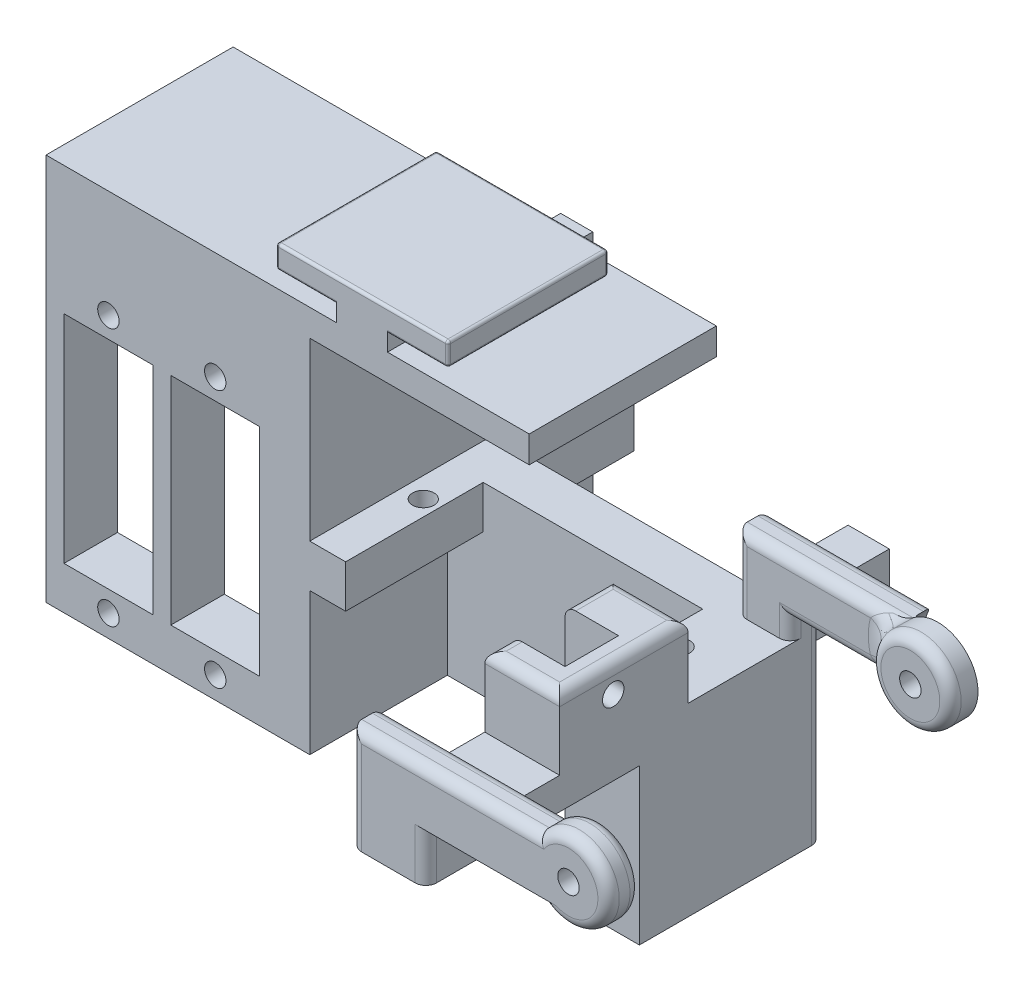
SolidWorks part; units mm, degrees
ref_plane "Front Plane" through (0, 0, 0) normal (0, 0, 1) x (1, 0, 0)
ref_plane "Top Plane" through (0, 0, 0) normal (0, 1, 0) x (1, 0, 0)
ref_plane "Right Plane" through (0, 0, 0) normal (1, 0, 0) x (0, 0, -1)
sketch "Sketch1" plane through (0, 0, 0) normal (0, 0, 1) x (1, 0, 0)
  line L1 (-10.82, 18.1) -> (10.82, 18.1)
  line L2 (-10.82, 18.1) -> (-10.82, -18.1)
  line L3 (-10.82, -18.1) -> (10.82, -18.1)
  line L4 (10.82, 18.1) -> (10.82, -18.1)
  line L5 (-10.82, 18.1) -> (10.82, -18.1) construction
  line L6 (-10.82, -18.1) -> (10.82, 18.1) construction
  point P0 (0, 0)
  dimension "D1" = 21.64
  dimension "D2" = 36.2
extrude "Center Column" add sketch "Sketch1" along normal mid plane 5
sketch "Sketch2" plane through (-10.82, 0, 0) normal (-1, 0, 0) x (0, 0, 1)
  line L0 (-2.5, 18.1) -> (-14.98, 18.1)
  line L1 (-14.98, 18.1) -> (-14.98, 15.6)
  line L2 (-14.98, 15.6) -> (-10.5, 15.6)
  line L3 (-10.5, 15.6) -> (-2.5, 10.98)
  line L4 (-2.5, 18.1) -> (-2.5, -18.1) construction
  line L6 (-2.5, 10.98) -> (2.5, 10.98)
  line L7 (2.5, 18.1) -> (2.5, -18.1) construction
  line L8 (2.5, 10.98) -> (2.5, 18.1)
  line L9 (2.5, 18.1) -> (-2.5, 18.1)
  dimension "D1" = 12.48
  dimension "D2" = 2.5
  dimension "D3" = 4.48
  dimension "D4" = 7.12
extrude "Column Cap" add sketch "Sketch2" against normal blind 55.14
sketch "Sketch5" plane through (0, 0, 2.5) normal (0, 0, 1) x (1, 0, 0)
  line L0 (16.33, 18.1) -> (21.08, 18.1)
  line L1 (44.32, 18.1) -> (-10.82, 18.1) construction
  line L2 (21.08, 18.1) -> (21.08, 19.6)
  line L3 (21.08, 19.6) -> (26.74, 19.6)
  line L4 (26.74, 19.6) -> (26.74, 21.75)
  line L5 (26.74, 21.75) -> (10.67, 21.75)
  line L6 (10.67, 21.75) -> (10.67, 19.6)
  line L7 (10.67, 19.6) -> (16.33, 19.6)
  line L8 (16.33, 19.6) -> (16.33, 18.1)
  dimension "D1" = 4.75
  dimension "D2" = 5.66
  dimension "D3" = 5.66
  dimension "D4" = 2.15
  dimension "D5" = 1.5
  dimension "D6" = 2.15
  dimension "D7" = 27.15
extrude "Attachment Block" add sketch "Sketch5" against normal blind 14.98
sketch "Sketch6" plane through (10.82, 0, 0) normal (1, 0, 0) x (0, 0, -1)
  line L0 (-2.5, -18.1) -> (-2.5, -3.6)
  line L1 (-2.5, -18.1) -> (-2.5, 10.98) construction
  line L2 (-2.5, -3.6) -> (2.5, -3.6)
  line L3 (2.5, -18.1) -> (2.5, 10.98) construction
  line L4 (2.5, -3.6) -> (2.5, -18.1)
  line L5 (2.5, -18.1) -> (-2.5, -18.1)
  dimension "D1" = 14.5
extrude "Central Extrusion" add sketch "Sketch6" along normal blind 33.792
sketch "Sketch7" plane through (0, 0, -2.5) normal (0, 0, -1) x (-1, 0, 0)
  line L0 (-10.82, -3.6) -> (-10.82, -0.8181)
  line L1 (-10.82, -3.6) -> (-10.82, 10.98) construction
  line L4 (-34.92, -0.8181) -> (-10.82, -0.8181)
  line L6 (-44.612, -18.1) -> (-10.82, -18.1)
  line L7 (10.82, -18.1) -> (-44.612, -18.1) construction
  line L8 (-10.82, -18.1) -> (-10.82, -3.6)
  line L10 (-44.612, -3.6) -> (-10.82, -3.6) construction
  line L11 (-34.92, -0.8181) -> (-44.612, -0.8181)
  line L12 (-44.612, -0.8181) -> (-44.612, -18.1)
  line L13 (-44.612, -18.1) -> (-40.254, -18.1)
  line M10 (-10.82, 10.98) -> (-10.82, -3.6)
  line M11 (-10.82, -3.6) -> (-44.612, -3.6)
  dimension "D1" = 24.1
  dimension "D2" = 2.7819
  dimension "D3" = 4.358
extrude "Wing Extrusion" add sketch "Sketch7" along normal mid plane 0.89 contours L4 M11 M10 | L6 L8 M11 region at (27.716, -2.2091, -2.5) region at (27.716, -10.85, -2.5)
sketch "Sketch10" plane through (0, 0, -2.945) normal (0, 0, -1) x (-1, 0, 0)
  line L0 (-10.82, -0.8181) -> (-10.82, -9.8181)
  line L1 (-10.82, -9.8181) -> (-14.67, -9.8181)
  line L2 (-14.67, -9.8181) -> (-14.67, -0.8181)
  line L3 (-10.82, -0.8181) -> (-44.612, -0.8181) construction
  line L4 (-14.67, -0.8181) -> (-10.82, -0.8181)
  dimension "D1" = 9
  dimension "D2" = 3.85
extrude "Servo Tab Extrusion" add sketch "Sketch10" along normal blind 9.48
sketch "Sketch11" plane through (0, 0, -2.945) normal (0, 0, -1) x (-1, 0, 0)
  line L0 (-44.612, -0.8181) -> (-44.612, -18.1)
  line L1 (-14.67, -0.8181) -> (-44.612, -0.8181) construction
  line L2 (-44.612, -18.1) -> (-10.82, -18.1) construction
  line L3 (-44.612, -18.1) -> (-34.67, -18.1)
  line L4 (-34.67, -18.1) -> (-34.67, -0.8181)
  line L5 (-34.67, -0.8181) -> (-44.612, -0.8181)
  dimension "D1" = 20
  dimension "D2" = 0
extrude "Front Tab Extrusion" add sketch "Sketch11" along normal blind 11.63
sketch "Sketch15" plane through (0, 0, -2.055) normal (0, 0, 1) x (1, 0, 0)
  line L0 (37.612, -3.6) -> (47.612, -3.6)
  line L1 (10.82, -3.6) -> (44.612, -3.6) construction
  line L2 (47.612, -3.6) -> (47.612, 5.9)
  line L3 (47.612, 5.9) -> (37.612, 5.9)
  line L4 (37.612, 5.9) -> (37.612, -3.6)
  dimension "D1" = 7
  dimension "D2" = 10
  dimension "D3" = 9.5
extrude "Center Block" add sketch "Sketch15" along normal blind 12
sketch "Sketch16" plane through (37.612, 0, 0) normal (-1, 0, 0) x (0, 0, 1)
  line L0 (2.445, 5.9) -> (2.445, 0.47)
  line L1 (9.945, 5.9) -> (-2.055, 5.9) construction
  line L2 (2.445, 0.47) -> (7.445, 0.47)
  line L3 (7.445, 0.47) -> (7.445, 5.9)
  line L4 (2.445, 5.9) -> (7.445, 5.9)
  line L5 (-2.055, 5.9) -> (-2.055, -0.8181) construction
  dimension "D1" = 4.5
  dimension "D2" = 5
  dimension "D3" = 5.43
extrude "Center Chasm" cut sketch "Sketch16" against normal blind 5
sketch "Sketch17" plane through (42.612, 0, 0) normal (-1, 0, 0) x (0, 0, 1)
  line L0 (7.445, 5.9) -> (2.445, 5.9) construction
  line L1 (2.445, 5.9) -> (2.445, 0.47) construction
  circle A0 centre (4.945, 3.4) radius 1
  dimension "D1" = 2
  dimension "D2" = 2.5
  dimension "D3" = 2.5
extrude "Center Hole" cut sketch "Sketch17" against normal through all
sketch "Sketch18" plane through (0, 0, 9.945) normal (0, 0, 1) x (1, 0, 0)
  line L1 (47.612, -3.6) -> (47.612, 5.9) construction
  line L2 (47.612, -0.6488) -> (37.612, -0.6488)
  line L3 (37.612, 5.9) -> (37.612, -3.6) construction
  line L4 (37.612, -0.6488) -> (37.612, -3.6)
  line L6 (37.612, -3.6) -> (47.612, -3.6)
  line L7 (47.612, -3.6) -> (47.612, -0.6488)
  dimension "D1" = 2.9512
extrude "Holder Arm" add sketch "Sketch18" along normal blind 12.5
sketch "Sketch19" plane through (0, -0.6488, 0) normal (0, 1, 0) x (1, 0, 0)
  line L1 (37.612, -22.445) -> (37.612, -9.945) construction
  line L7 (37.612, -19.445) -> (37.612, -22.445)
  line L8 (37.612, -22.445) -> (47.612, -22.445)
  line L11 (37.612, -19.445) -> (47.612, -19.445)
  line L12 (47.612, -19.445) -> (47.612, -22.445)
  line L13 (47.612, -22.445) -> (47.612, -9.945) construction
  dimension "D1" = 3
extrude "Elbow Extrusion" add sketch "Sketch19" along normal blind 6.78
sketch "Sketch27" plane through (47.612, 0, 0) normal (1, 0, 0) x (0, 0, -1)
  line L0 (-22.445, 6.1312) -> (-22.445, 1.1312)
  line L1 (-22.445, -3.6) -> (-22.445, 6.1312) construction
  line L2 (-22.445, 1.1312) -> (-19.445, 1.1312)
  line L3 (-19.445, 6.1312) -> (-19.445, -0.6488) construction
  line L4 (-19.445, 1.1312) -> (-19.445, 6.1312)
  line L5 (-19.445, 6.1312) -> (-22.445, 6.1312)
  dimension "D1" = 5
extrude "Forearm Extrusion" add sketch "Sketch27" along normal blind 7.874
sketch "Sketch28" plane through (0, 0, 22.445) normal (0, 0, 1) x (1, 0, 0)
  circle A0 centre (57.932, 3.6312) radius 1
  circle A1 centre (57.932, 3.6312) radius 3.75
  dimension "D1" = 2
  dimension "D4" = 7.5
  dimension "D2" = 20.32
  dimension "D3" = 2.5
extrude "Hand Extrusion" add sketch "Sketch28" against normal up to surface (3 mm away) up to face at (46.9033, 2.2045, 19.445)
sketch "Sketch23" plane through (0, -0.8181, 0) normal (0, 1, 0) x (1, 0, 0)
  line L1 (44.612, 14.575) -> (39.612, 14.575)
  line L2 (44.612, 14.575) -> (44.612, 11.575)
  line L3 (44.612, 11.575) -> (39.612, 11.575)
  line L4 (39.612, 14.575) -> (39.612, 11.575)
  dimension "D1" = 5
  dimension "D2" = 3
extrude "Right Elbow Extrusion" add sketch "Sketch23" along normal blind 6.902
sketch "Sketch24" plane through (44.612, 0, 0) normal (1, 0, 0) x (0, 0, -1)
  line L0 (11.575, 6.0839) -> (14.575, 6.0839)
  line L1 (14.575, 6.0839) -> (14.575, 1.0839)
  line L2 (14.575, 6.0839) -> (14.575, -18.1) construction
  line L3 (14.575, 1.0839) -> (11.575, 1.0839)
  line L4 (11.575, 6.0839) -> (11.575, -0.8181) construction
  line L5 (11.575, 1.0839) -> (11.575, 6.0839)
  dimension "D1" = 5
extrude "Right Forearm Extrusion" add sketch "Sketch24" along normal blind 11
sketch "Sketch25" plane through (0, 0, -14.575) normal (0, 0, -1) x (-1, 0, 0)
  line L1 (-34.67, -18.1) -> (-34.67, -0.8181) construction
  circle A0 centre (-57.87, 3.5839) radius 1
  circle A1 centre (-57.87, 3.5839) radius 3.75
  dimension "D2" = 2
  dimension "D4" = 7.5
  dimension "D1" = 23.2
  dimension "D3" = 2.5
extrude "Right Hand" add sketch "Sketch25" against normal blind 5.02
sketch "Sketch26" plane through (0, 0, -2.5) normal (0, 0, -1) x (-1, 0, 0)
  line L0 (10.82, 10.98) -> (10.82, -18.1) construction
  line L1 (0.84, 6.1) -> (9.14, 6.1)
  line L2 (0.84, 6.1) -> (0.84, -14.1)
  line L3 (0.84, -14.1) -> (9.14, -14.1)
  line L4 (9.14, 6.1) -> (9.14, -14.1)
  line L5 (-9.14, 6.1) -> (-0.84, 6.1)
  line L6 (-9.14, 6.1) -> (-9.14, -14.1)
  line L7 (-9.14, -14.1) -> (-0.84, -14.1)
  line L8 (-0.84, 6.1) -> (-0.84, -14.1)
  line L9 (10.82, 10.98) -> (-10.82, 10.98) construction
  circle A0 centre (-4.99, 8.05) radius 1
  circle A1 centre (4.99, 8.05) radius 1
  circle A2 centre (-4.99, -16.05) radius 1
  circle A3 centre (4.99, -16.05) radius 1
  dimension "D9" = 2
  dimension "D10" = 2
  dimension "D11" = 2
  dimension "D12" = 2
  dimension "D1" = 1.68
  dimension "D2" = 4.88
  dimension "D3" = 20.2
  dimension "D4" = 8.3
  dimension "D5" = 1.68
  dimension "D6" = 8.3
  dimension "D7" = 4.88
  dimension "D8" = 20.2
  dimension "D13" = 4.15
  dimension "D14" = 1.95
  dimension "D15" = 1.95
  dimension "D16" = 4.15
  dimension "D17" = 1.95
  dimension "D18" = 4.15
  dimension "D19" = 1.95
  dimension "D20" = 4.15
extrude "Rear Servo Mounts" cut sketch "Sketch26" against normal through all
sketch "Sketch29" plane through (10.82, 0, 0) normal (1, 0, 0) x (0, 0, -1)
  line L1 (-2.5, 10.98) -> (19.745, 10.98)
  line L2 (2.945, -18.1) -> (19.745, -18.1)
  line L3 (19.745, -18.1) -> (19.745, 10.98)
  line L4 (-2.5, 10.98) -> (-2.5, -18.1)
  line L5 (-2.5, -18.1) -> (2.945, -18.1)
  dimension "D2" = 16.8
extrude "New Back" add sketch "Sketch29" along normal blind 3
sketch "Sketch30" plane through (0, -18.1, 0) normal (0, -1, 0) x (1, 0, 0)
  line L10 (10.82, -19.745) -> (13.82, -19.745)
  line L11 (10.82, -19.745) -> (13.82, -19.745)
  line L12 (13.82, -19.745) -> (13.82, -2.945)
  line L13 (13.82, -19.745) -> (13.82, -2.945)
  line L14 (44.612, 2.5) -> (-10.82, 2.5)
  line L19 (-10.82, 2.5) -> (-10.82, -2.5)
  line L20 (-10.82, -2.5) -> (10.82, -2.5)
  line L21 (10.82, -2.5) -> (10.82, -19.745)
  line L24 (13.82, -2.945) -> (34.67, -2.945)
  line L25 (34.67, -2.945) -> (34.67, -14.575)
  line L26 (34.67, -14.575) -> (44.612, -14.575)
  line L27 (44.612, -14.575) -> (44.612, 2.5)
  line L28 (44.612, 2.5) -> (-10.82, 2.5)
  line L33 (-10.82, 2.5) -> (-10.82, -2.5)
  line L34 (-10.82, -2.5) -> (10.82, -2.5)
  line L35 (10.82, -2.5) -> (10.82, -19.745)
  line L38 (13.82, -2.945) -> (34.67, -2.945)
  line L39 (34.67, -2.945) -> (34.67, -14.575)
  line L40 (34.67, -14.575) -> (44.612, -14.575)
  line L41 (44.612, -14.575) -> (44.612, 2.5)
  dimension "D1" = 0
extrude "Bottom Support" add sketch "Sketch30" along normal blind 3
sketch "Sketch31" plane through (34.67, 0, 0) normal (-1, 0, 0) x (0, 0, 1)
  line L0 (-14.575, -0.8181) -> (-2.945, -0.8181)
  line L1 (-2.945, -0.8181) -> (-2.945, -21.1)
  line L2 (-2.945, -21.1) -> (-14.575, -21.1)
  line L3 (-14.575, -21.1) -> (-14.575, -0.8181)
extrude "Re-cut Central Cavity" cut sketch "Sketch31" against normal blind 3
sketch "Sketch32" plane through (14.67, 0, 0) normal (1, 0, 0) x (0, 0, -1)
  line L4 (2.945, -0.8181) -> (2.945, -9.8181)
  line L5 (2.945, -9.8181) -> (12.425, -9.8181)
  line L6 (12.425, -9.8181) -> (12.425, -0.8181)
  line L7 (12.425, -0.8181) -> (2.945, -0.8181)
  line L8 (2.945, -0.8181) -> (2.945, -9.8181)
  line L9 (2.945, -9.8181) -> (12.425, -9.8181)
  line L10 (12.425, -9.8181) -> (12.425, -0.8181)
  line L11 (12.425, -0.8181) -> (2.945, -0.8181)
  dimension "D1" = 0
extrude "Form Left Front-Rear Block" add sketch "Sketch32" along normal blind 3
sketch "Sketch33" plane through (0, 0, -2.945) normal (0, 0, -1) x (-1, 0, 0)
  line L0 (-37.67, -0.8181) -> (-37.67, -18.1)
  line L1 (-37.67, -21.1) -> (-37.67, -0.8181) construction
  line L2 (-37.67, -0.8181) -> (-17.67, -0.8181)
  line L3 (-17.67, -0.8181) -> (-17.67, -18.1)
  line L4 (-17.67, -18.1) -> (-37.67, -18.1)
  dimension "D1" = 3
extrude "Create Center Cavity" cut sketch "Sketch33" against normal through all
sketch "Sketch34" plane through (13.82, 0, 0) normal (1, 0, 0) x (0, 0, -1)
  line L0 (12.425, -0.8181) -> (2.055, -0.8181) construction
  line L1 (12.425, -0.8181) -> (10.355, -0.8181)
  line L2 (12.425, -0.8181) -> (12.425, -21.1)
  line L6 (10.355, -0.8181) -> (10.355, -21.1)
  line L7 (19.745, -21.1) -> (2.945, -21.1) construction
  line L8 (10.355, -21.1) -> (12.425, -21.1)
  dimension "D1" = 8.3
  dimension "D2" = 0
extrude "Boss-Extrude6" add sketch "Sketch34" along normal up to surface (23.85 mm away) up to face at (37.67, -9.7838, 1.4217)
sketch "Sketch35" plane through (0, 0, -12.425) normal (0, 0, -1) x (-1, 0, 0)
  line L0 (-13.82, -0.8181) -> (-13.82, -21.1)
  line L4 (-13.82, 10.98) -> (-13.82, -0.8181)
  line L6 (-13.82, 10.98) -> (-10.82, 10.98)
  line L7 (-10.82, 10.98) -> (-10.82, -21.1)
  line L8 (-10.82, -21.1) -> (-13.82, -21.1)
  dimension "D1" = 3
extrude "Extend Wing Extrusion" add sketch "Sketch35" along normal blind 10.6532
sketch "Sketch37" plane through (0, 0, -12.425) normal (0, 0, -1) x (-1, 0, 0)
  line L0 (-13.82, -0.8181) -> (-13.82, -9.8181)
  line L1 (-13.82, -21.1) -> (-13.82, -0.8181) construction
  line L2 (-13.82, -9.8181) -> (-17.67, -9.8181)
  line L3 (-17.67, -9.8181) -> (-17.67, -0.8181)
  line L4 (-13.82, -0.8181) -> (-37.67, -0.8181) construction
  line L5 (-17.67, -0.8181) -> (-13.82, -0.8181)
  dimension "D1" = 9
  dimension "D2" = 3.85
extrude "Right Front-Rear Extrusion" add sketch "Sketch37" along normal blind 9.48
sketch "Sketch38" plane through (0, 5.9, 0) normal (0, 1, 0) x (1, 0, 0)
  line L0 (47.612, -9.945) -> (47.612, 2.055)
  line L1 (47.612, 2.055) -> (44.612, 2.055)
  line L2 (47.612, 2.055) -> (37.612, 2.055) construction
  line L3 (44.612, 2.055) -> (44.612, -9.945)
  line L4 (47.612, -9.945) -> (37.612, -9.945) construction
  line L5 (44.612, -9.945) -> (47.612, -9.945)
  dimension "D1" = 3
extrude "Trim Center Block" cut sketch "Sketch38" against normal up to surface (6.5488 mm away) up to face at (42.612, -0.6488, 14.695)
sketch "Sketch39" plane through (0, 0, -14.575) normal (0, 0, -1) x (-1, 0, 0)
  line L0 (-37.67, -0.8181) -> (-37.67, -9.8181)
  line L1 (-37.67, -0.8181) -> (-37.67, -21.1) construction
  line L2 (-37.67, -9.8181) -> (-41.52, -9.8181)
  line L3 (-41.52, -9.8181) -> (-41.52, -0.8181)
  line L4 (-41.52, -0.8181) -> (-37.67, -0.8181)
  dimension "D1" = 9
  dimension "D2" = 3.85
extrude "Right Front Extension" add sketch "Sketch39" along normal up to surface (7.33 mm away) up to face at (15.745, -5.3181, -21.905)
sketch "Sketch40" plane through (0, -3.6, 0) normal (0, -1, 0) x (1, 0, 0)
  line L0 (44.612, 2.5) -> (44.612, -2.055)
  line L1 (44.612, -2.055) -> (47.612, -2.055)
  line L2 (47.612, -2.055) -> (47.612, 22.445)
  line L3 (47.612, 22.445) -> (44.612, 22.445)
  line L4 (37.67, 22.445) -> (47.612, 22.445) construction
  line L5 (44.612, 22.445) -> (44.612, 2.5)
extrude "Trim Left Arm" cut sketch "Sketch40" against normal up to surface (4.7312 mm away) up to face at (51.3745, 1.1312, 20.945)
sketch "Sketch42" plane through (0, 0, -2.945) normal (0, 0, -1) x (-1, 0, 0)
  line L0 (-37.67, -21.1) -> (-37.67, -18.1)
  line L1 (-37.67, -18.1) -> (-13.82, -18.1)
  line L2 (-13.82, -9.8181) -> (-13.82, -21.1) construction
  line L3 (-13.82, -18.1) -> (-13.82, -21.1)
  line L4 (-13.82, -21.1) -> (-37.67, -21.1)
extrude "Close Base Plate" add sketch "Sketch42" along normal up to surface (7.41 mm away) up to face at (23.0533, -10.5787, -10.355)
sketch "Sketch43" plane through (17.67, 0, 0) normal (1, 0, 0) x (0, 0, -1)
  line L0 (2.945, -9.8181) -> (-2.5, -9.8181)
  line L1 (-2.5, -3.6) -> (-2.5, -18.1) construction
  line L2 (-2.5, -9.8181) -> (-2.5, -18.1)
  line L3 (-2.5, -18.1) -> (2.945, -18.1)
  line L4 (2.945, -18.1) -> (2.945, -9.8181)
extrude "Shape Left Front Block" cut sketch "Sketch43" against normal up to surface (3.85 mm away) up to face at (13.82, -13.9591, -6.65)
sketch "Sketch44" plane through (0, -3.6, 0) normal (0, 1, 0) x (1, 0, 0)
  line L4 (13.82, -2.5) -> (17.67, -2.5)
  line L5 (17.67, -2.5) -> (17.67, 2.055)
  line L6 (17.67, 2.055) -> (13.82, 2.055)
  line L7 (13.82, 2.055) -> (13.82, -2.5)
  line L8 (13.82, -2.5) -> (17.67, -2.5)
  line L9 (17.67, -2.5) -> (17.67, 2.055)
  line L10 (17.67, 2.055) -> (13.82, 2.055)
  line L11 (13.82, 2.055) -> (13.82, -2.5)
  dimension "D1" = 0
extrude "Fix Left Front Chip" add sketch "Sketch44" along normal up to surface (2.7819 mm away) up to face at (31.2805, -0.8181, -12.1063)
sketch "Sketch45" plane through (0, 0, -21.905) normal (0, 0, -1) x (-1, 0, 0)
  line L0 (-13.82, -9.8181) -> (-13.82, -21.1)
  line L4 (-41.52, -0.8181) -> (-41.52, -9.8181)
  line L5 (-41.52, -9.8181) -> (-37.67, -9.8181)
  line L6 (-37.67, -9.8181) -> (-37.67, -0.8181)
  line L7 (-37.67, -0.8181) -> (-41.52, -0.8181)
  line L8 (-41.52, -0.8181) -> (-41.52, -9.8181)
  line L9 (-41.52, -9.8181) -> (-37.67, -9.8181)
  line L10 (-37.67, -9.8181) -> (-37.67, -0.8181)
  line L11 (-37.67, -0.8181) -> (-41.52, -0.8181)
  line L12 (-13.82, -0.8181) -> (-17.67, -0.8181)
  line L13 (-17.67, -0.8181) -> (-17.67, -9.8181)
  line L14 (-17.67, -9.8181) -> (-13.82, -9.8181)
  line L15 (-13.82, -9.8181) -> (-13.82, -0.8181)
  line L16 (-13.82, -0.8181) -> (-17.67, -0.8181)
  line L17 (-17.67, -0.8181) -> (-17.67, -9.8181)
  line L18 (-17.67, -9.8181) -> (-13.82, -9.8181)
  line L22 (-13.82, 10.98) -> (-13.82, -21.1)
  line L25 (-13.82, -21.1) -> (-10.82, -21.1)
  line L26 (-10.82, -21.1) -> (-10.82, 10.98)
  line L27 (-10.82, 10.98) -> (-13.82, 10.98)
  line L28 (-13.82, 10.98) -> (-13.82, -0.8181)
  line L31 (-13.82, -21.1) -> (-10.82, -21.1)
  line L32 (-10.82, -21.1) -> (-10.82, 10.98)
  line L33 (-10.82, 10.98) -> (-13.82, 10.98)
  dimension "D1" = 0
  dimension "D2" = 0
  dimension "D3" = 0
extrude "Adjust Front Mounting Block" add sketch "Sketch45" along normal blind 2.032
sketch "Sketch46" plane through (0, 0, -12.425) normal (0, 0, -1) x (-1, 0, 0)
  line L6 (-17.67, -9.8181) -> (-17.67, -0.8181)
  line L7 (-17.67, -0.8181) -> (-37.67, -0.8181)
  line L8 (-37.67, -0.8181) -> (-37.67, -21.1)
  line L9 (-37.67, -21.1) -> (-13.82, -21.1)
  line L10 (-13.82, -21.1) -> (-13.82, -9.8181)
  line L11 (-13.82, -9.8181) -> (-17.67, -9.8181)
  line L12 (-17.67, -9.8181) -> (-17.67, -0.8181)
  line L13 (-17.67, -0.8181) -> (-37.67, -0.8181)
  line L14 (-37.67, -0.8181) -> (-37.67, -21.1)
  line L15 (-37.67, -21.1) -> (-13.82, -21.1)
  line L16 (-13.82, -21.1) -> (-13.82, -9.8181)
  line L17 (-13.82, -9.8181) -> (-17.67, -9.8181)
  dimension "D1" = 0
extrude "Thicken Center Block" add sketch "Sketch46" along normal up to surface (2.15 mm away) up to face at (56.87, 3.5839, -14.575)
sketch "Sketch47" plane through (0, -0.8181, 0) normal (0, 1, 0) x (1, 0, 0)
  line L1 (37.67, 14.575) -> (37.67, 23.937) construction
  line L2 (17.67, 23.937) -> (17.67, 14.575) construction
  line L3 (37.67, 2.055) -> (37.67, 10.355) construction
  line L4 (17.67, 10.355) -> (17.67, -2.5) construction
  circle A0 centre (39.62, 18.725) radius 1
  circle A1 centre (15.72, 18.725) radius 1
  circle A2 centre (15.72, 6.205) radius 1
  circle A3 centre (39.62, 6.205) radius 1
  dimension "D1" = 2
  dimension "D2" = 2
  dimension "D3" = 2
  dimension "D4" = 2
  dimension "D5" = 4.15
  dimension "D6" = 4.15
  dimension "D7" = 4.15
  dimension "D8" = 4.15
  dimension "D9" = 1.95
  dimension "D10" = 1.95
  dimension "D11" = 1.95
  dimension "D12" = 1.95
extrude "Front Servo Mounts" cut sketch "Sketch47" against normal up to surface (9 mm away) up to face at (15.745, -9.8181, -3.9275)
fillet "Hand Fillets" radius 1 19 edges at (61.682, 3.6312, 22.445) (46.3745, 6.1312, 22.445) (37.612, 2.6565, 22.445) (44.612, -1.2344, 22.445) (37.612, 2.7412, 19.445) (46.3745, 6.1312, 19.445) (61.682, 3.6312, 19.445) (49.8745, 1.1312, 19.445) (44.612, 0.2412, 19.445) (39.612, 2.6329, -11.575) (44.612, 0.1329, -11.575) (49.8435, 1.0839, -11.575) (47.3435, 6.0839, -11.575) (54.12, 3.5839, -9.555) (44.612, -10.0081, -14.575) (39.612, 2.6329, -14.575) (49.8435, 1.0839, -14.575) (61.62, 3.5839, -14.575) (47.3435, 6.0839, -14.575)
fillet "Center Block Fillet" radius 1 5 edges at (41.112, 5.9, -2.055) (37.612, 5.9, 8.695) (37.612, 5.9, 0.195) (44.612, 5.9, 3.945) (41.112, 5.9, 9.945)
sketch "Sketch48" plane through (-10.82, 0, 0) normal (-1, 0, 0) x (0, 0, 1)
  line L0 (-10.5, 15.6) -> (-2.5, 10.98)
  line L1 (-2.5, 10.98) -> (-2.5, 15.6)
  line L2 (-2.5, 15.6) -> (-10.5, 15.6)
extrude "Cut-Extrude1" cut sketch "Sketch48" against normal up to surface (55.14 mm away) up to face at (44.32, 14.8933, -6.3267)
sketch "Sketch49" plane through (44.32, 0, 0) normal (1, 0, 0) x (0, 0, -1)
  line L0 (-2.5, 10.98) -> (2.5, 10.98)
  line L1 (2.5, 10.98) -> (2.5, 13.29)
  line L2 (2.5, 15.6) -> (2.5, 10.98) construction
  line L3 (2.5, 13.29) -> (-2.5, 13.29)
  line L4 (-2.5, 10.98) -> (-2.5, 18.1) construction
  line L5 (-2.5, 13.29) -> (-2.5, 10.98)
extrude "Cut-Extrude2" cut sketch "Sketch49" against normal up to vertex (30.5 mm away) up to point (13.82, 10.98, 2.5)
sketch "Sketch50" plane through (44.32, 0, 0) normal (1, 0, 0) x (0, 0, -1)
  line L6 (-2.5, 18.1) -> (-2.5, 13.29)
  line L7 (-2.5, 13.29) -> (2.5, 13.29)
  line L8 (2.5, 13.29) -> (2.5, 15.6)
  line L9 (2.5, 15.6) -> (14.98, 15.6)
  line L10 (14.98, 15.6) -> (14.98, 18.1)
  line L11 (14.98, 18.1) -> (-2.5, 18.1)
  line L12 (-2.5, 18.1) -> (-2.5, 13.29)
  line L13 (-2.5, 13.29) -> (2.5, 13.29)
  line L14 (2.5, 13.29) -> (2.5, 15.6)
  line L15 (2.5, 15.6) -> (14.98, 15.6)
  line L16 (14.98, 15.6) -> (14.98, 18.1)
  line L17 (14.98, 18.1) -> (-2.5, 18.1)
  dimension "D1" = 0
extrude "Cut-Extrude3" cut sketch "Sketch50" against normal blind 10
sketch "Sketch51" plane through (0, 0, -14.575) normal (0, 0, -1) x (-1, 0, 0)
  circle A0 centre (-57.87, 3.5839) radius 3.75
  dimension "D1" = 7.5
extrude "Cut-Extrude4" cut sketch "Sketch51" against normal blind 2.45
fillet "Fillet1" radius 1 1 edges at (54.12, 3.5839, -12.125)
sketch "Sketch52" plane through (0, -21.1, 0) normal (0, -1, 0) x (1, 0, 0)
  line L8 (13.82, -14.575) -> (43.612, -14.575)
  line L9 (44.612, -13.575) -> (44.612, 2.5)
  line L10 (44.612, 2.5) -> (-10.82, 2.5)
  line L11 (-10.82, 2.5) -> (-10.82, -2.5)
  line L12 (-10.82, -2.5) -> (10.82, -2.5)
  line L13 (10.82, -2.5) -> (10.82, -23.937)
  line L14 (10.82, -23.937) -> (13.82, -23.937)
  line L15 (13.82, -23.937) -> (13.82, -14.575)
  line L16 (13.82, -14.575) -> (43.612, -14.575)
  line L17 (44.612, -13.575) -> (44.612, 2.5)
  line L18 (44.612, 2.5) -> (-10.82, 2.5)
  line L19 (-10.82, 2.5) -> (-10.82, -2.5)
  line L20 (-10.82, -2.5) -> (10.82, -2.5)
  line L21 (10.82, -2.5) -> (10.82, -23.937)
  line L22 (10.82, -23.937) -> (13.82, -23.937)
  line L23 (13.82, -23.937) -> (13.82, -14.575)
  arc A1 (43.612, -14.575) -> (44.612, -13.575) centre (43.612, -13.575) ccw
  arc A2 (43.612, -14.575) -> (44.612, -13.575) centre (43.612, -13.575) ccw
  dimension "D1" = 0
extrude "Cut-Extrude5" cut sketch "Sketch52" against normal blind 3
fillet "Fillet2" radius 2.54 3 edges at (54.6146, 1.7224, -11.6426) (54.7781, 5.7058, -11.7919) (54.12, 3.5839, -11.575)
sketch "Sketch53" plane through (34.32, 0, 0) normal (1, 0, 0) x (0, 0, -1)
  line L0 (2.5, 15.6) -> (2.5, 13.29)
  line L1 (2.5, 13.29) -> (-2.5, 13.29)
  line L2 (-2.5, 13.29) -> (-2.5, 15.6)
  line L3 (-2.5, 18.1) -> (-2.5, 13.29) construction
  line L4 (-2.5, 15.6) -> (2.5, 15.6)
extrude "Cut-Extrude6" cut sketch "Sketch53" against normal up to surface (20.5 mm away) up to face at (13.82, 7.8173, -7.979)
fillet "Fillet3" radius 0.25 14 edges at (10.67, 20.675, -12.48) (13.5, 19.6, -12.48) (23.91, 19.6, -12.48) (26.74, 20.675, -12.48) (18.705, 21.75, -12.48) (26.74, 20.675, 2.5) (23.91, 19.6, 2.5) (13.5, 19.6, 2.5) (18.705, 21.75, 2.5) (10.67, 20.675, 2.5) (10.67, 19.6, -4.99) (10.67, 21.75, -4.99) (26.74, 19.6, -4.99) (26.74, 21.75, -4.99)
sketch "Sketch54" plane through (0, -9.8181, 0) normal (0, -1, 0) x (1, 0, 0)
  line L4 (37.67, -14.575) -> (37.67, -23.937)
  line L5 (37.67, -23.937) -> (41.52, -23.937)
  line L6 (41.52, -23.937) -> (41.52, -14.575)
  line L7 (41.52, -14.575) -> (37.67, -14.575)
  line L8 (37.67, -14.575) -> (37.67, -23.937)
  line L9 (37.67, -23.937) -> (41.52, -23.937)
  line L10 (41.52, -23.937) -> (41.52, -14.575)
  line L11 (41.52, -14.575) -> (37.67, -14.575)
  line L12 (17.67, -23.937) -> (17.67, -14.575)
  line L13 (17.67, -14.575) -> (13.82, -14.575)
  line L14 (13.82, -14.575) -> (13.82, -23.937)
  line L15 (13.82, -23.937) -> (17.67, -23.937)
  line L16 (17.67, -23.937) -> (17.67, -14.575)
  line L17 (17.67, -14.575) -> (13.82, -14.575)
  line L18 (13.82, -14.575) -> (13.82, -23.937)
  line L19 (13.82, -23.937) -> (17.67, -23.937)
  line L20 (13.82, -10.355) -> (17.67, -10.355)
  line L21 (17.67, -10.355) -> (17.67, 2.5)
  line L22 (17.67, 2.5) -> (13.82, 2.5)
  line L23 (13.82, 2.5) -> (13.82, -10.355)
  line L24 (13.82, -10.355) -> (17.67, -10.355)
  line L25 (17.67, -10.355) -> (17.67, 2.5)
  line L26 (17.67, 2.5) -> (13.82, 2.5)
  line L27 (13.82, 2.5) -> (13.82, -10.355)
  dimension "D1" = 0
  dimension "D2" = 0
  dimension "D3" = 0
extrude "Cut-Extrude9" cut sketch "Sketch54" against normal blind 5
sketch "Sketch55" plane through (17.67, 0, 0) normal (1, 0, 0) x (0, 0, -1)
  line L4 (-2.5, -0.8181) -> (-2.5, -4.8181)
  line L5 (-2.5, -4.8181) -> (10.355, -4.8181)
  line L6 (10.355, -4.8181) -> (10.355, -0.8181)
  line L7 (10.355, -0.8181) -> (-2.5, -0.8181)
  line L8 (-2.5, -0.8181) -> (-2.5, -4.8181)
  line L9 (-2.5, -4.8181) -> (10.355, -4.8181)
  line L10 (10.355, -4.8181) -> (10.355, -0.8181)
  line L11 (10.355, -0.8181) -> (-2.5, -0.8181)
  dimension "D1" = 0
extrude "Cut-Extrude10" cut sketch "Sketch55" against normal blind 0.5
